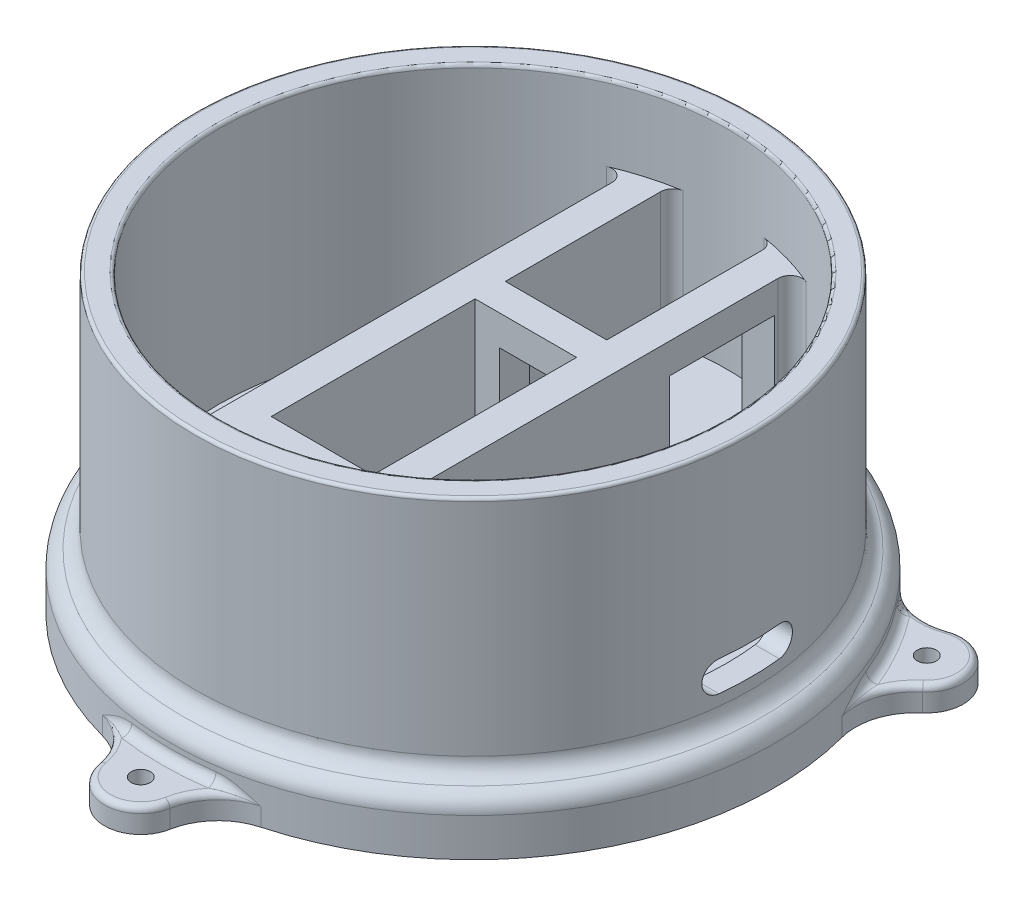
SolidWorks part; units mm, degrees
ref_plane "Front Plane" through (0, 0, 0) normal (0, 0, 1) x (1, 0, 0)
ref_plane "Top Plane" through (0, 0, 0) normal (0, 1, 0) x (1, 0, 0)
ref_plane "Right Plane" through (0, 0, 0) normal (1, 0, 0) x (0, 0, -1)
sketch "Sketch1" plane through (0, 0, 0) normal (0, 1, 0) x (1, 0, 0)
  circle A0 centre (0, 0) radius 63.5
extrude "Boss-Extrude1" add sketch "Sketch1" along normal blind 6.35
sketch "Sketch2" plane through (0, 6.35, 0) normal (0, 1, 0) x (1, 0, 0)
  circle A0 centre (0, 0) radius 58.42
  circle A1 centre (0, 0) radius 53.34
  dimension "D1" = 116.84
extrude "Boss-Extrude2" add sketch "Sketch2" along normal blind 50.8
fillet "Fillet1" radius 3.81 1 edges at (0, 6.35, 58.42)
fillet "Fillet2" radius 3.81 1 edges at (0, 6.35, 63.5)
sketch "Sketch3" plane through (0, 6.35, 0) normal (0, 1, 0) x (1, 0, 0)
  line L0 (-17.4625, 50.4006) -> (-17.4625, -50.4006)
  line L1 (0, -31.4325) -> (0, 31.4325) construction
  line L2 (17.4625, 50.4006) -> (17.4625, -50.4006)
  circle A0 centre (0, 0) radius 53.34 construction
  circle A1 centre (0, 0) radius 53.34 construction
  arc A2 (-17.4625, -50.4006) -> (17.4625, -50.4006) centre (0, 0) ccw
  arc A3 (17.4625, 50.4006) -> (-17.4625, 50.4006) centre (0, 0) ccw
  dimension "D1" = 17.4625
sketch "Sketch4" plane through (0, 0, 0) normal (1, 0, 0) x (0, 0, -1)
  line L0 (-6.35, 15.6493) -> (6.35, 15.6493) construction
  line L1 (0, 10.3534) -> (0, -10.3534) construction
  line L2 (-6.35, 18.8243) -> (6.35, 18.8243)
  line L3 (-6.35, 12.4743) -> (6.35, 12.4743)
  arc A0 (-6.35, 18.8243) -> (-6.35, 12.4743) centre (-6.35, 15.6493) ccw
  arc A1 (6.35, 12.4743) -> (6.35, 18.8243) centre (6.35, 15.6493) ccw
  point P4 (0, 15.6493)
  dimension "D1" = 12.7
  dimension "D2" = 6.35
extrude "Cut-Extrude1" cut sketch "Sketch4" along normal through all
sketch "Sketch5" plane through (0, 0, 0) normal (0, -1, 0) x (1, 0, 0)
  circle A0 centre (0, 0) radius 63.5
extrude "Boss-Extrude4" add sketch "Sketch5" along normal blind 5.08
sketch "Sketch6" plane through (0, -5.08, 0) normal (0, -1, 0) x (1, 0, 0)
  line L0 (0, 49.5462) -> (0, 69.85) construction
  line L1 (0, -31.4325) -> (0, 31.4325) construction
  line L2 (-7.62, 63.0411) -> (-7.62, 69.85)
  line L3 (7.62, 63.0411) -> (7.62, 69.85)
  line L4 (50.7852, -38.1197) -> (56.6819, -41.5241)
  line L5 (58.4052, -24.9215) -> (64.3019, -28.3259)
  line L6 (-58.4052, -24.9215) -> (-64.3019, -28.3259)
  line L7 (-50.7852, -38.1197) -> (-56.6819, -41.5241)
  arc A1 (7.62, 69.85) -> (-7.62, 69.85) centre (0, 69.85) ccw
  arc A2 (7.62, 63.0411) -> (-7.62, 63.0411) centre (0, 0) ccw
  circle A3 centre (0, 0) radius 63.5 construction
  circle A4 centre (0, 69.85) radius 2
  arc A5 (56.6819, -41.5241) -> (64.3019, -28.3259) centre (60.4919, -34.925) ccw
  arc A6 (50.7852, -38.1197) -> (58.4052, -24.9215) centre (0, 0) ccw
  circle A7 centre (60.4919, -34.925) radius 2
  arc A8 (-64.3019, -28.3259) -> (-56.6819, -41.5241) centre (-60.4919, -34.925) ccw
  arc A9 (-58.4052, -24.9215) -> (-50.7852, -38.1197) centre (0, 0) ccw
  circle A10 centre (-60.4919, -34.925) radius 2
  point P5 (0, 59.6981)
  point P29 (0, 0)
  dimension "D1" = 7.62
  dimension "D3" = 4
  dimension "D2" = 69.85
  dimension "D4" = 3
extrude "Boss-Extrude6" add sketch "Sketch6" against normal blind 5.08
fillet "Fillet3" radius 12.7 1 edges at (58.4052, -2.54, -24.9215)
fillet "Fillet4" radius 12.7 5 edges at (7.62, -2.54, 63.0411) (-7.62, -2.54, 63.0411) (-58.4052, -2.54, -24.9215) (-50.7852, -2.54, -38.1197) (50.7852, -2.54, -38.1197)
extrude "Boss-Extrude7" add sketch "Sketch3" along normal blind 6.35
sketch "Sketch8" plane through (0, 12.7, 0) normal (0, 1, 0) x (1, 0, 0)
  line L0 (-10.668, 52.2623) -> (-10.668, 17.4625)
  line L1 (0, -34.2265) -> (0, 34.2265) construction
  line L2 (10.668, 52.2623) -> (10.668, 17.4625)
  line L3 (-17.4625, 50.4006) -> (-17.4625, -50.4006)
  line L4 (-17.4625, 50.4006) -> (-17.4625, -50.4006) construction
  line L5 (17.4625, 50.4006) -> (17.4625, -50.4006)
  line L6 (17.4625, -50.4006) -> (17.4625, 50.4006) construction
  line L7 (-10.668, -31.75) -> (10.668, -31.75)
  line L8 (-34.2265, 0) -> (34.2265, 0) construction
  line L9 (-10.668, 11.1125) -> (10.668, 11.1125)
  line L10 (-10.668, 17.4625) -> (10.668, 17.4625)
  line L11 (-10.668, -38.1) -> (10.668, -38.1)
  line L12 (-10.668, -38.1) -> (-10.668, -52.2623)
  line L13 (10.668, -38.1) -> (10.668, -52.2623)
  line L14 (-10.668, 11.1125) -> (-10.668, -31.75)
  line L15 (10.668, 11.1125) -> (10.668, -31.75)
  arc A0 (17.4625, 50.4006) -> (-17.4625, 50.4006) centre (0, 0) ccw construction
  circle A1 centre (0, 0) radius 53.34 construction
  arc A2 (-17.4625, -50.4006) -> (-10.668, -52.2623) centre (0, 0) ccw
  arc A3 (17.4625, 50.4006) -> (10.668, 52.2623) centre (0, 0) ccw
  arc A4 (10.668, -52.2623) -> (17.4625, -50.4006) centre (0, 0) ccw
  arc A5 (-10.668, 52.2623) -> (-17.4625, 50.4006) centre (0, 0) ccw
  dimension "D1" = 10.668
  dimension "D2" = 31.75
  dimension "D3" = 11.1125
  dimension "D4" = 6.35
  dimension "D5" = 6.35
extrude "Boss-Extrude8" add sketch "Sketch8" along normal blind 28.575
sketch "Sketch12" plane through (10.668, 0, 0) normal (-1, 0, 0) x (0, 0, 1)
  line L0 (-34.8624, 12.7) -> (-34.8624, 41.275) construction
  line L1 (-52.2623, 12.7) -> (-17.4625, 12.7) construction
  line L2 (-52.2623, 41.275) -> (-17.4625, 41.275) construction
  line L3 (-17.4625, 26.9875) -> (-52.2623, 26.9875) construction
  line L4 (-17.4625, 41.275) -> (-17.4625, 12.7) construction
  line L5 (-52.2623, 41.275) -> (-52.2623, 12.7) construction
  line L7 (-45.9123, 34.925) -> (-23.8125, 34.925)
  line L8 (-45.9123, 34.925) -> (-45.9123, 19.05)
  line L9 (-45.9123, 19.05) -> (-23.8125, 19.05)
  line L10 (-23.8125, 34.925) -> (-23.8125, 19.05)
  line L11 (-45.9123, 34.925) -> (-23.8125, 19.05) construction
  line L12 (-45.9123, 19.05) -> (-23.8125, 34.925) construction
  point P12 (-34.8624, 26.9875)
  dimension "D1" = 6.35
  dimension "D2" = 6.35
extrude "Cut-Extrude3" cut sketch "Sketch12" against normal blind 7.62
fillet "Fillet8" radius 1.27 3 edges at (-61.553, 0, -23.254) (-67.091, 0, -38.735) (-50.9151, 0, -41.6795)
fillet "Fillet9" radius 1.27 6 edges at (50.9151, 0, -41.6795) (67.091, 0, -38.735) (61.553, 0, -23.254) (10.6379, 0, 64.9335) (0, 0, 77.47) (-10.6379, 0, 64.9335)
fillet "Fillet11" radius 1.905 3 edges at (60.6276, -0.3858, -18.8823) (46.6664, -0.3858, -43.0639) (54.9926, 0, -31.75)
fillet "Fillet12" radius 1.905 6 edges at (-46.6664, -0.3858, -43.0639) (-60.6276, -0.3858, -18.8823) (-13.9612, -0.3858, 61.9462) (13.9612, -0.3858, 61.9462) (-54.9926, 0, -31.75) (0, 0, 63.5)
fillet "Fillet16" radius 0.635 2 edges at (0, 57.15, 53.34) (0, 57.15, 58.42)
fillet "Fillet18" radius 2.54 1 edges at (17.4625, 23.8125, 50.4006)
fillet "Fillet19" radius 2.54 7 edges at (-17.4625, 23.8125, -50.4006) (-10.668, 26.9875, -52.2623) (10.668, 26.9875, -52.2623) (17.4625, 23.8125, -50.4006) (-17.4625, 23.8125, 50.4006) (-10.668, 26.9875, 52.2623) (10.668, 26.9875, 52.2623)
sketch "Sketch14" plane through (10.668, 0, 0) normal (-1, 0, 0) x (0, 0, 1)
  line L0 (-45.9123, 19.05) -> (-23.8125, 19.05)
  line L1 (-45.9123, 19.05) -> (-45.9123, 12.6381)
  line L2 (-23.8125, 19.05) -> (-23.8125, 12.6381)
  line L3 (-45.9123, 12.6381) -> (-23.8125, 12.6381)
extrude "Cut-Extrude4" cut sketch "Sketch14" against normal blind 7.62
sketch "Sketch15" plane through (0, 0, -17.4625) normal (0, 0, -1) x (-1, 0, 0)
  line L0 (-5.588, 12.7) -> (5.588, 12.7)
  line L1 (-5.588, 12.7) -> (-5.588, 34.925)
  line L2 (5.588, 12.7) -> (5.588, 34.925)
  line L3 (-5.588, 34.925) -> (5.588, 34.925)
  line L4 (-10.668, 12.7) -> (10.668, 12.7) construction
  line L5 (10.668, 41.275) -> (10.668, 12.7) construction
  line L7 (-10.668, 41.275) -> (-10.668, 12.7) construction
  line L8 (-10.668, 41.275) -> (10.668, 41.275) construction
  dimension "D1" = 5.08
  dimension "D2" = 5.08
  dimension "D3" = 6.35
extrude "Cut-Extrude5" cut sketch "Sketch15" against normal blind 7.62
